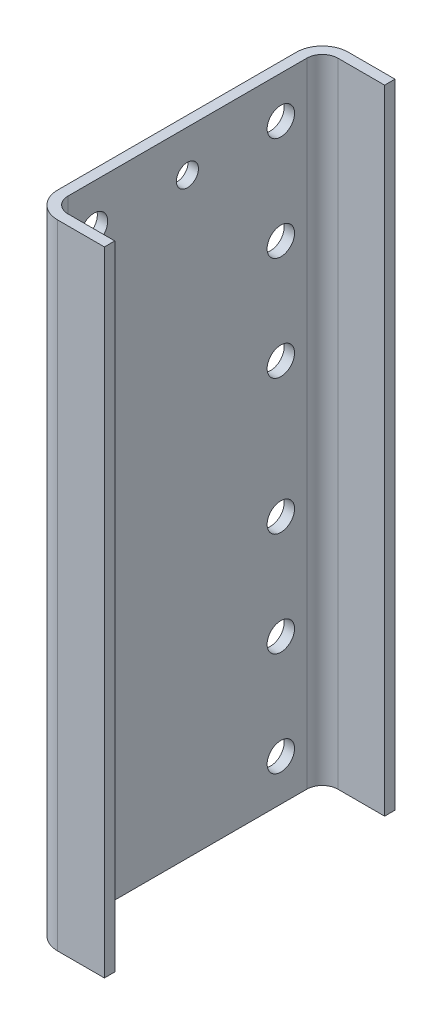
SolidWorks part; units mm, degrees
material "ASTM A36"
ref_plane "Front" through (0, 0, 0) normal (0, 0, 1) x (1, 0, 0)
ref_plane "Top" through (0, 0, 0) normal (0, 1, 0) x (1, 0, 0)
ref_plane "Side" through (0, 0, 0) normal (1, 0, 0) x (0, 0, -1)
sketch "Sketch1" plane through (0, 0, 0) normal (0, 1, 0) x (0, 0, -1)
  line L0 (-73.025, 0) -> (73.025, 0)
  line L1 (88.9, -15.875) -> (88.9, -44.45)
  line L2 (88.9, -44.45) -> (82.55, -44.45)
  line L3 (82.55, -44.45) -> (82.55, -15.875)
  line L4 (73.025, -6.35) -> (-73.025, -6.35)
  line L5 (0, 46.7552) -> (0, -80.6904) construction
  line L6 (-82.55, -44.45) -> (-82.55, -15.875)
  line L7 (-88.9, -44.45) -> (-82.55, -44.45)
  line L8 (-88.9, -15.875) -> (-88.9, -44.45)
  arc A0 (73.025, 0) -> (88.9, -15.875) centre (73.025, -15.875) cw
  arc A1 (82.55, -15.875) -> (73.025, -6.35) centre (73.025, -15.875) ccw
  arc A2 (-82.55, -15.875) -> (-73.025, -6.35) centre (-73.025, -15.875) cw
  arc A3 (-73.025, 0) -> (-88.9, -15.875) centre (-73.025, -15.875) ccw
  point P18 (0, -6.35)
  point P20 (0, 0)
  dimension "D2" = 9.525
  dimension "D1" = 6.35
  dimension "D3" = 44.45
  dimension "D4" = 177.8
extrude "Base-Extrude" add sketch "Sketch1" along normal blind 193.675 and the other way blind 193.675
sketch "Sketch2" plane through (0, 0, 0) normal (1, 0, 0) x (0, 0, -1)
  line L0 (0, 215.1923) -> (0, -215.7073) construction
  line L1 (57.15, 168.275) -> (57.15, 104.775) construction
  line L2 (57.15, 104.775) -> (57.15, 41.275) construction
  line L3 (73.025, 193.675) -> (73.025, -193.675) construction
  line L4 (57.15, 41.275) -> (57.15, -41.275) construction
  line L5 (57.15, -41.275) -> (57.15, -104.775) construction
  line L6 (57.15, -104.775) -> (57.15, -168.275) construction
  line L9 (57.15, 168.275) -> (0, 168.275) construction
  circle A0 centre (57.15, 41.275) radius 8.382
  circle A1 centre (57.15, 104.775) radius 8.382
  circle A2 centre (57.15, 168.275) radius 8.382
  circle A3 centre (57.15, -41.275) radius 8.382
  circle A4 centre (57.15, -104.775) radius 8.382
  circle A5 centre (57.15, -168.275) radius 8.382
  circle A6 centre (-57.15, -168.275) radius 8.382
  circle A7 centre (-57.15, -104.775) radius 8.382
  circle A8 centre (-57.15, -41.275) radius 8.382
  circle A9 centre (-57.15, 41.275) radius 8.382
  circle A10 centre (-57.15, 104.775) radius 8.382
  circle A11 centre (-57.15, 168.275) radius 8.382
  circle A12 centre (0, 168.275) radius 6.731
  dimension "D2" = 127
  dimension "D3" = 16.764
  dimension "D4" = 57.15
  dimension "D7" = 127
  dimension "D8" = 13.462
  dimension "D1" = 41.275
  dimension "D5" = 15.875
  dimension "D6" = 41.275
extrude "Holes" cut sketch "Sketch2" along normal through all
ref_plane "Plane1" through (-431.8, 0, 0) normal (1, 0, 0) x (0, 0, -1)
sketch "Frame Drilling Sketch" plane through (-431.8, 0, 0) normal (1, 0, 0) x (0, 0, -1)
  line L0 (-57.15, 168.275) -> (57.15, 168.275) construction
  line L1 (57.15, 168.275) -> (57.15, 104.775) construction
  line L2 (57.15, 104.775) -> (57.15, 41.275) construction
  line L3 (57.15, 41.275) -> (57.15, -41.275) construction
  line L4 (57.15, -41.275) -> (57.15, -104.775) construction
  line L5 (57.15, -104.775) -> (57.15, -168.275) construction
  line L6 (57.15, -168.275) -> (-57.15, -168.275) construction
  line L7 (-57.15, -168.275) -> (-57.15, -104.775) construction
  line L8 (-57.15, -104.775) -> (-57.15, -41.275) construction
  line L9 (-57.15, -41.275) -> (-57.15, 41.275) construction
  line L10 (-57.15, 41.275) -> (-57.15, 104.775) construction
  line L11 (-57.15, 104.775) -> (-57.15, 168.275) construction
  line L12 (-57.15, 104.775) -> (57.15, 104.775) construction
  line L13 (-57.15, 41.275) -> (57.15, 41.275) construction
  line L14 (-57.15, -41.275) -> (57.15, -41.275) construction
  line L15 (-57.15, -104.775) -> (57.15, -104.775) construction
  circle A0 centre (57.15, 168.275) radius 8.382 construction
  circle A1 centre (57.15, 104.775) radius 8.382 construction
  circle A2 centre (57.15, 41.275) radius 8.382 construction
  circle A3 centre (57.15, -41.275) radius 8.382 construction
  circle A4 centre (57.15, -104.775) radius 8.382 construction
  circle A5 centre (57.15, -168.275) radius 8.382 construction
  circle A6 centre (-57.15, -168.275) radius 8.382 construction
  circle A7 centre (-57.15, -104.775) radius 8.382 construction
  circle A8 centre (-57.15, -41.275) radius 8.382 construction
  circle A9 centre (-57.15, 41.275) radius 8.382 construction
  circle A10 centre (-57.15, 104.775) radius 8.382 construction
  circle A11 centre (-57.15, 168.275) radius 8.382 construction
  circle A12 centre (57.15, 168.275) radius 8.382
  circle A13 centre (57.15, 104.775) radius 8.382
  circle A14 centre (57.15, 41.275) radius 8.382
  circle A15 centre (57.15, -41.275) radius 8.382
  circle A16 centre (57.15, -104.775) radius 8.382
  circle A17 centre (57.15, -168.275) radius 8.382
  circle A18 centre (-57.15, -168.275) radius 8.382
  circle A19 centre (-57.15, -104.775) radius 8.382
  circle A20 centre (-57.15, -41.275) radius 8.382
  circle A21 centre (-57.15, 41.275) radius 8.382
  circle A22 centre (-57.15, 104.775) radius 8.382
  circle A23 centre (-57.15, 168.275) radius 8.382
